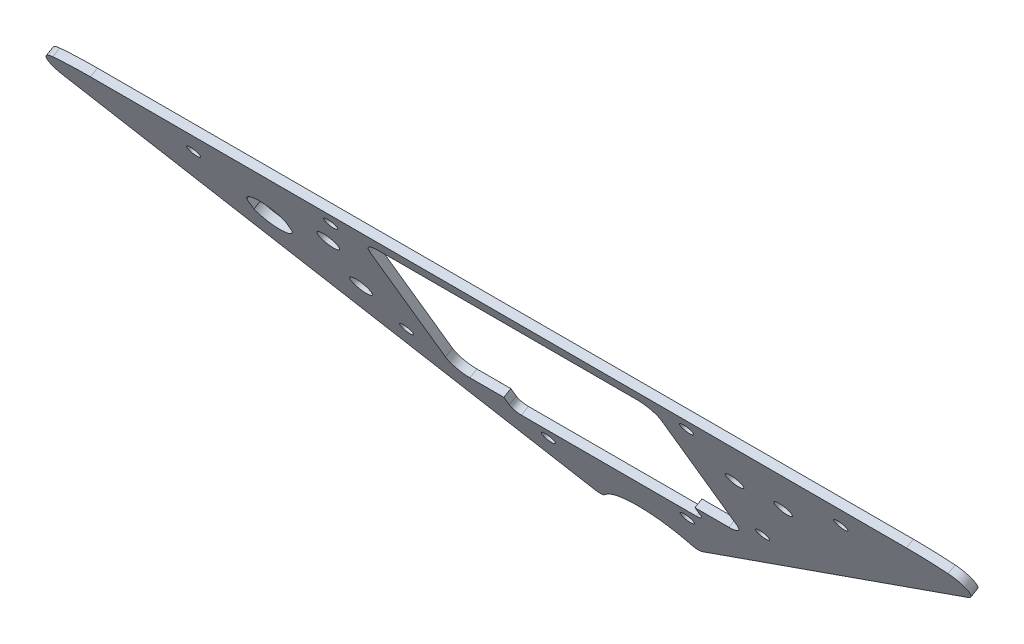
SolidWorks part; units mm, degrees
material "Thornel VCB-20 Carbon Cloth"
ref_plane "Front Plane" through (0, 0, 0) normal (0, 0, 1) x (1, 0, 0)
ref_plane "Top Plane" through (0, 0, 0) normal (0, 1, 0) x (1, 0, 0)
ref_plane "Right Plane" through (0, 0, 0) normal (1, 0, 0) x (0, 0, -1)
ref_plane "Plane1" through (0, -119.0262, 202.5184) normal (0, 0.5067, -0.8621) x (-1, 0, 0)
ref_axis "Axis1" through (-138.1707, 616.7078, 646.8636) along (0.8355, -0.4738, -0.2785)
sketch "Sketch2" plane through (0, -119.0262, 202.5184) normal (0, 0.5067, -0.8621) x (-1, 0, 0)
  line L0 (21.0542, 782.405) -> (177.8755, 885.5596)
  line L1 (138.1707, 859.4424) -> (70.4504, 814.8971) construction
  line L2 (0, 1972.2008) -> (0, -1972.2008) construction
  line L5 (0, 898.6914) -> (0, 768.5559) construction
  line L7 (160.0992, 922.5039) -> (160.0992, 897.1039) construction
  line L9 (160.0992, 898.6914) -> (-160.0992, 898.6914)
  line L10 (-160.0992, 897.1039) -> (160.0992, 897.1039) construction
  line L11 (-21.0542, 782.405) -> (-177.8755, 885.5596)
  arc A0 (16.8957, 782.9949) -> (-16.8957, 782.9949) centre (0, 768.5559) ccw
  circle A3 centre (-127, 884.165) radius 2.4892
  circle A4 centre (-27.2422, 806.1914) radius 2.4892
  circle A5 centre (27.2422, 806.1914) radius 2.4892
  circle A6 centre (127, 884.165) radius 2.4892
  arc A7 (160.0992, 898.6914) -> (175.6846, 897.0805) centre (160.0992, 822.4914) cw
  arc A8 (175.6846, 897.0805) -> (177.8755, 885.5596) centre (174.3858, 890.8648) cw
  arc A9 (-160.0992, 898.6914) -> (-175.6846, 897.0805) centre (-160.0992, 822.4914) ccw
  arc A10 (-175.6846, 897.0805) -> (-177.8755, 885.5596) centre (-174.3858, 890.8648) ccw
  arc A11 (21.0542, 782.405) -> (16.8957, 782.9949) centre (19.3094, 785.0576) cw
  arc A12 (-21.0542, 782.405) -> (-16.8957, 782.9949) centre (-19.3094, 785.0576) ccw
  point P11 (181.7577, 900.9366)
  point P37 (18.5681, 780.7697)
  point P40 (-18.5681, 780.7697)
  dimension "D1" = 22.225
  dimension "D2" = 1.5875
  dimension "D3" = 6.35
  dimension "D4" = 4.9784
  dimension "D5" = 76.2
  dimension "D6" = 3.175
extrude "Boss-Extrude1" add sketch "Sketch2" along normal blind 3.175
sketch "Sketch4" plane through (0, -117.4174, 199.7812) normal (0, 0.5067, -0.8621) x (-1, 0, 0)
  circle A0 centre (-69.85, 890.7539) radius 2.4892
  circle A1 centre (-69.85, 832.0164) radius 2.4892
  circle A2 centre (69.85, 832.0164) radius 2.4892
  circle A3 centre (69.85, 890.7539) radius 2.4892
  dimension "D1" = 4.9784
extrude "Cut-Extrude1" cut sketch "Sketch4" against normal through all
sketch "Sketch6" plane through (0, -119.0262, 202.5184) normal (0, -0.5067, 0.8621) x (1, 0, 0)
  circle A0 centre (-79.654, 873.2914) radius 4
  circle A1 centre (-79.654, 847.8914) radius 4
  dimension "D1" = 8
extrude "Cut-Extrude3" cut sketch "Sketch6" against normal through all
sketch "Sketch5" plane through (0, -117.4174, 199.7812) normal (0, 0.5067, -0.8621) x (-1, 0, 0)
  line L1 (21.0542, 782.405) -> (177.8755, 885.5596) construction
  line L2 (99.2157, 862.57) -> (99.2157, 868.1378)
  line L3 (114.2157, 868.1378) -> (114.2157, 862.57)
  line L5 (160.0992, 898.6914) -> (-160.0992, 898.6914) construction
  arc A0 (99.2157, 862.57) -> (114.2157, 862.57) centre (106.7157, 865.3539) ccw
  arc A1 (114.2157, 868.1378) -> (99.2157, 868.1378) centre (106.7157, 865.3539) ccw
  point P1 (0, 0)
  point P3 (79.654, 873.2914)
  point P4 (101.7057, 865.8587)
  dimension "D1" = 16
  dimension "D3" = 22.225
  dimension "D2" = 33.3375
  dimension "D4" = 15
extrude "Cut-Extrude2" cut sketch "Sketch5" against normal through all
sketch "Sketch7" plane through (0, -117.4174, 199.7812) normal (0, 0.5067, -0.8621) x (-1, 0, 0)
  line L0 (-69.85, 890.7539) -> (-69.85, 832.0164) construction
  line L1 (-80.925, 861.2352) -> (-73.025, 861.2352) construction
  line L2 (-80.925, 861.2352) -> (-80.925, 874.2352) construction
  line L3 (-80.925, 874.2352) -> (-73.025, 874.2352) construction
  line L4 (-73.025, 861.2352) -> (-73.025, 874.2352) construction
  line L5 (-80.925, 861.2352) -> (-73.025, 874.2352) construction
  line L6 (-80.925, 874.2352) -> (-73.025, 861.2352) construction
  line L7 (-92.075, 861.2352) -> (-99.975, 861.2352) construction
  line L8 (-92.075, 861.2352) -> (-92.075, 874.2352) construction
  line L9 (-92.075, 874.2352) -> (-99.975, 874.2352) construction
  line L10 (-99.975, 861.2352) -> (-99.975, 874.2352) construction
  line L11 (-92.075, 861.2352) -> (-99.975, 874.2352) construction
  line L12 (-92.075, 874.2352) -> (-99.975, 861.2352) construction
  circle A0 centre (-69.85, 890.7539) radius 2.4892 construction
  circle A1 centre (-76.975, 867.7352) radius 3.2639
  circle A2 centre (-96.025, 867.7352) radius 3.2639
  point P0 (-76.975, 867.7352)
  point P5 (-96.025, 867.7352)
  point P10 (-69.85, 861.3852)
  point P21 (-70.625, 862.4536)
  dimension "D5" = 6.5278
  dimension "D1" = 13
  dimension "D2" = 7.9
  dimension "D3" = 19.05
  dimension "D4" = 3.175
  dimension "D6" = 6.35
extrude "Cut-Extrude4" cut sketch "Sketch7" against normal through all
sketch "Sketch8" plane through (0, -117.4174, 199.7812) normal (0, 0.5067, -0.8621) x (-1, 0, 0)
  line L1 (50.825, 891.6039) -> (-50.825, 891.6039)
  line L2 (57.175, 885.2539) -> (57.175, 826.8039)
  line L3 (50.825, 820.4539) -> (37.5, 820.4539)
  line L4 (-57.175, 885.2539) -> (-57.175, 826.8039)
  line L5 (57.175, 891.6039) -> (-57.175, 820.4539) construction
  line L6 (57.175, 820.4539) -> (-57.175, 891.6039) construction
  line L7 (-55.5875, 890.0164) -> (-55.5875, 822.0414) construction
  line L8 (55.5875, 822.0414) -> (55.5875, 890.0164) construction
  line L9 (-55.5875, 822.0414) -> (55.5875, 822.0414) construction
  line L10 (55.5875, 890.0164) -> (-55.5875, 890.0164) construction
  line L11 (-37.5, 816.2874) -> (-37.5, 820.4539)
  line L12 (-37.5, 813.1124) -> (-37.5, 817.8749) construction
  line L13 (37.5, 820.4539) -> (37.5, 816.2874)
  line L14 (34.325, 813.1124) -> (-34.325, 813.1124)
  line L15 (-37.5, 820.4539) -> (-50.825, 820.4539)
  arc A0 (-50.825, 820.4539) -> (-57.175, 826.8039) centre (-50.825, 826.8039) cw
  arc A1 (57.175, 826.8039) -> (50.825, 820.4539) centre (50.825, 826.8039) cw
  arc A2 (50.825, 891.6039) -> (57.175, 885.2539) centre (50.825, 885.2539) cw
  arc A3 (-50.825, 891.6039) -> (-57.175, 885.2539) centre (-50.825, 885.2539) ccw
  arc A4 (37.5, 816.2874) -> (34.325, 813.1124) centre (34.325, 816.2874) cw
  arc A5 (-37.5, 816.2874) -> (-34.325, 813.1124) centre (-34.325, 816.2874) ccw
  point P0 (0, 856.0289)
  point P34 (37.5, 813.1124)
  point P37 (-37.5, 813.1124)
  dimension "D5" = 6.35
  dimension "D6" = 3.175
  dimension "D1" = 1.5875
  dimension "D2" = 1.5875
  dimension "D3" = 1.5875
  dimension "D4" = 1.5875
extrude "Cut-Extrude5" cut sketch "Sketch8" against normal through all
